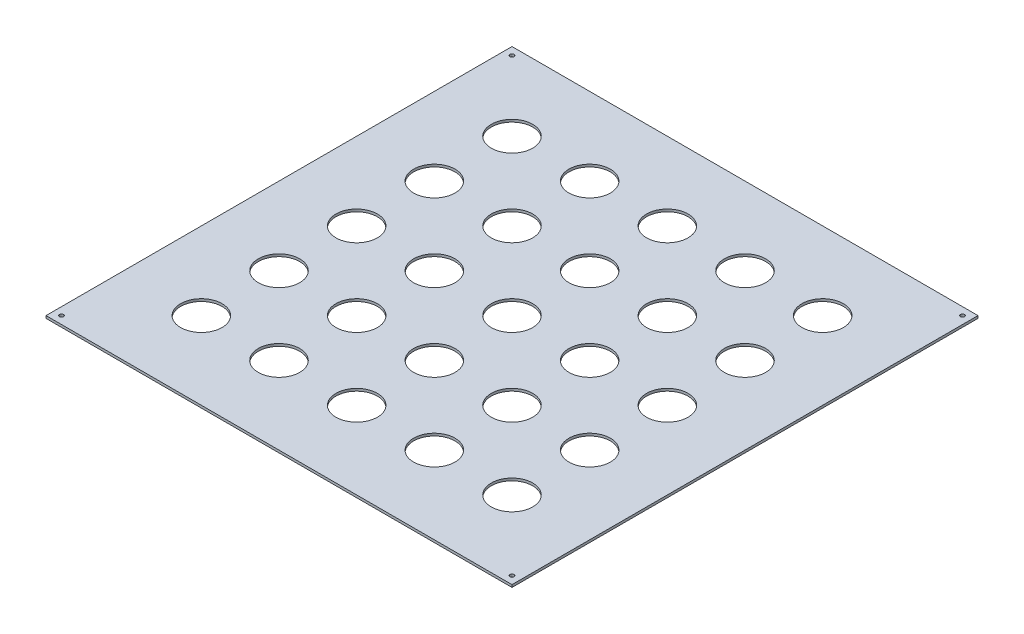
SolidWorks part; units mm, degrees
ref_plane "Front Plane" through (0, 0, 0) normal (0, 0, 1) x (1, 0, 0)
ref_plane "Top Plane" through (0, 0, 0) normal (0, 1, 0) x (1, 0, 0)
ref_plane "Right Plane" through (0, 0, 0) normal (1, 0, 0) x (0, 0, -1)
sketch "Sketch1" plane through (0, 0, 0) normal (0, 1, 0) x (1, 0, 0)
  line L0 (-290, 300) -> (-290, 290) construction
  line L1 (-300, -300) -> (300, -300)
  line L2 (-300, -300) -> (-300, 300)
  line L3 (-300, 300) -> (300, 300)
  line L4 (300, -300) -> (300, 300)
  line L5 (-300, -300) -> (300, 300) construction
  line L6 (-300, 300) -> (300, -300) construction
  line L7 (0, -55) -> (0, 55) construction
  line L8 (-55, 0) -> (55, 0) construction
  circle A0 centre (-290, 290) radius 2.6
  circle A1 centre (290, 290) radius 2.6
  circle A2 centre (290, -290) radius 2.6
  circle A3 centre (-290, -290) radius 2.6
  circle A6 centre (0, 0) radius 26.67
  circle A7 centre (100, 0) radius 26.67
  circle A8 centre (200, 0) radius 26.67
  circle A9 centre (100, 100) radius 26.67
  circle A10 centre (200, 100) radius 26.67
  circle A11 centre (100, 200) radius 26.67
  circle A12 centre (200, 200) radius 26.67
  circle A13 centre (0, 100) radius 26.67
  circle A14 centre (0, 200) radius 26.67
  circle A15 centre (-100, 0) radius 26.67
  circle A16 centre (-200, 0) radius 26.67
  circle A17 centre (-100, -100) radius 26.67
  circle A18 centre (-200, -100) radius 26.67
  circle A19 centre (-100, -200) radius 26.67
  circle A20 centre (-200, -200) radius 26.67
  circle A21 centre (0, -100) radius 26.67
  circle A22 centre (0, -200) radius 26.67
  circle A23 centre (200, -200) radius 26.67
  circle A24 centre (100, -200) radius 26.67
  circle A25 centre (200, -100) radius 26.67
  circle A26 centre (100, -100) radius 26.67
  circle A27 centre (-200, 200) radius 26.67
  circle A28 centre (-100, 200) radius 26.67
  circle A29 centre (-200, 100) radius 26.67
  circle A30 centre (-100, 100) radius 26.67
  point P0 (0, 0)
  dimension "D4" = 5.2
  dimension "D5" = 53.34
  dimension "D6" = 3
  dimension "D7" = 3
  dimension "D1" = 45
  dimension "D2" = 600
  dimension "D3" = 10
  dimension "D" = 10
  dimension "D8" = 3
  dimension "D9" = 3
extrude "Boss-Extrude1" add sketch "Sketch1" along normal blind 1.5875 and the other way blind 1.5875
